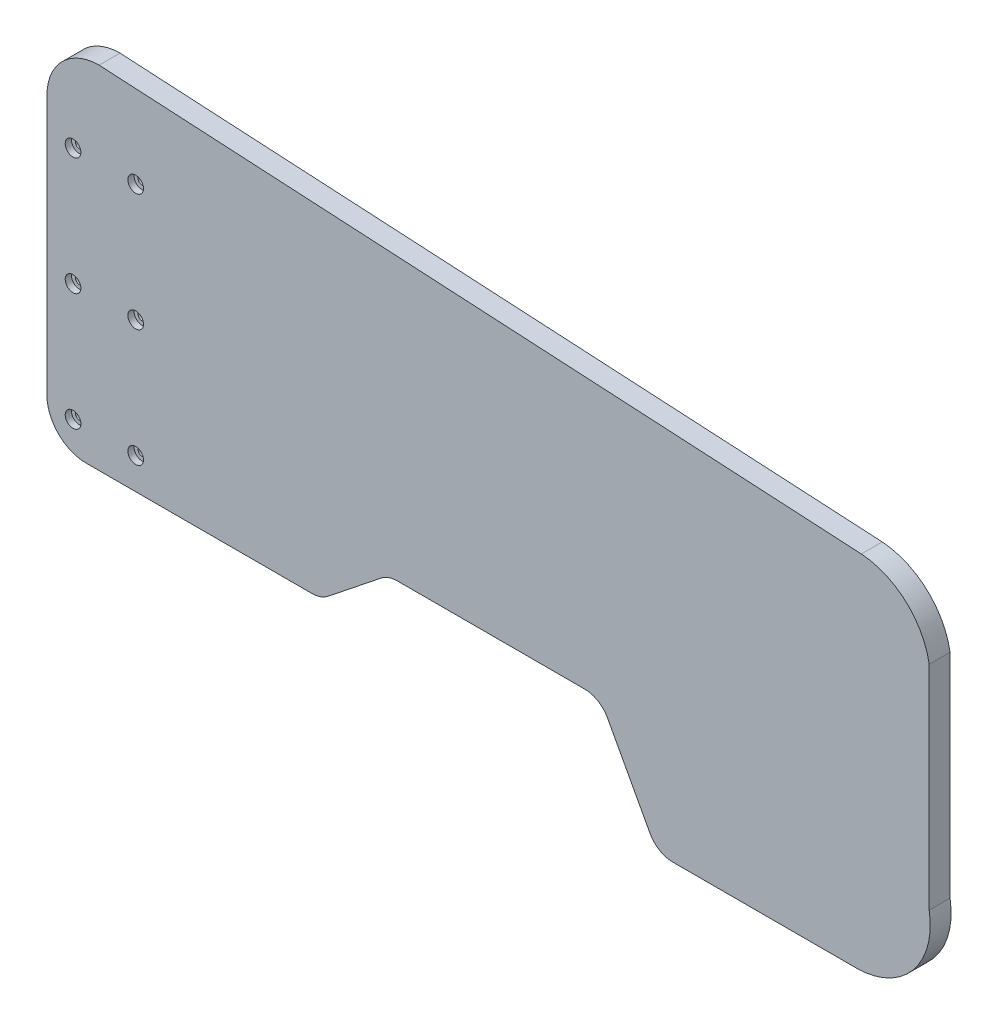
SolidWorks part; units mm, degrees
other "Folder spoin"
material "ABS PC"
ref_plane "Płaszczyzna przednia" through (0, 0, 0) normal (0, 0, 1) x (1, 0, 0)
ref_plane "Płaszczyzna górna" through (0, 0, 0) normal (0, 1, 0) x (1, 0, 0)
ref_plane "Płaszczyzna prawa" through (0, 0, 0) normal (1, 0, 0) x (0, 0, -1)
sketch "outer-wire" plane through (0, 0, 0) normal (0, 0, 1) x (1, 0, 0)
  line L0 (-24, -24.5302) -> (62.5, -24.5302)
  line L3 (-39, -9.5302) -> (-39, 90)
  line L4 (95.2361, -4) -> (167, -4)
  line L6 (176, -9.6411) -> (192, -39.2805)
  line L7 (68.7361, -22.3476) -> (89, -6.1826)
  line L10 (271, -44.5302) -> (200.7997, -44.5302)
  line L12 (299, -11.3778) -> (299, 70.2365)
  line L14 (-19, 110) -> (273, 93.8273)
  arc A0 (-39, -9.5302) -> (-24, -24.5302) centre (-24, -9.5302) ccw
  arc A1 (-19, 110) -> (-39, 90) centre (-19, 90) ccw
  arc A2 (62.5, -24.5302) -> (68.7361, -22.3476) centre (62.5, -14.5302) ccw
  arc A3 (89, -6.1826) -> (95.2361, -4) centre (95.2361, -14) cw
  arc A4 (271, -44.5302) -> (299, -11.3778) centre (271, -16.1298) ccw
  arc A5 (299, 70.2365) -> (273, 93.8273) centre (271, 65.5) ccw
  arc A6 (200.7997, -44.5302) -> (192, -39.2805) centre (200.7997, -34.5302) cw
  arc A7 (176, -9.6411) -> (167, -4) centre (167, -14) ccw
  point P14 (66, -24.5302)
  dimension "D2" = 20
  dimension "D1" = 15
  dimension "D7" = 66
  dimension "D8" = 89
  dimension "D10" = 167
  dimension "D17" = 271
  dimension "D18" = 273
  dimension "D20" = 39
  dimension "D21" = 110
  dimension "D4" = 28.4004
  dimension "D6" = 62.5
  dimension "D9" = 167
  dimension "D12" = 192
  dimension "D11" = 176
  dimension "D3" = 10
  dimension "D5" = 28.3978
  dimension "D13" = 65.5
  dimension "D14" = 4
  dimension "D15" = 71.7639
  dimension "D16" = 271
  dimension "D19" = 299
extrude "Dodanie-wyciągnięcie1" add sketch "outer-wire" along normal blind 8 contours L0 A2 L7 A3 L4 A7 L6 A6 L10 A4 L12 A5 L14 A1 L3 A0
ref_plane "Płaszczyzna6" through (0, -24.5302, 0) normal (0, -1, 0) x (-1, 0, 0)
sketch "Szkic1" plane through (0, -24.5302, 0) normal (0, -1, 0) x (-1, 0, 0)
  line L0 (24, 0) -> (-62.5, 0) construction
  line L1 (24, -8) -> (24, 0) construction
  circle A0 centre (19, 0) radius 3.5
  dimension "D1" = 7
  dimension "D2" = 5
extrude "Wytnij-wyciągnięcie1" cut sketch "Szkic1" against normal blind 100
ref_plane "Płaszczyzna12" through (0, 0, 8) normal (0, 0, 1) x (1, 0, 0)
sketch "Szkic3" plane through (0, 0, 8) normal (0, 0, 1) x (1, 0, 0)
  circle A2 centre (-5, 77.5) radius 1.5
  circle A3 centre (-29, 77.5) radius 1.5
  circle A4 centre (-29, -12.5) radius 1.5
  circle A5 centre (-29, 32.5) radius 1.5
  circle A6 centre (-5, 32.5) radius 1.5
  circle A7 centre (-5, -12.5) radius 1.5
  dimension "D6" = 45
  dimension "D2" = 12.5
  dimension "D3" = 24
  dimension "D4" = 45
  dimension "D5" = 45
  dimension "D7" = 5
extrude "Wytnij-wyciągnięcie3" cut sketch "Szkic3" along direction (0, 0, 1) on the side against the normal blind 5 contours A4 | A5 | A3 | A2 | A6 | A7
ref_plane "Płaszczyzna13" through (0, 0, 8) normal (0, 0, 1) x (1, 0, 0)
sketch "Szkic5" plane through (0, 0, 8) normal (0, 0, 1) x (1, 0, 0)
  circle A0 centre (-29, -12.5) radius 3
  circle A1 centre (-29, 32.5) radius 3
  circle A2 centre (-29, 77.5) radius 3
  circle A3 centre (-5, 77.5) radius 3
  circle A4 centre (-5, 32.5) radius 3
  circle A5 centre (-5, -12.5) radius 3
  dimension "D2" = 24
  dimension "D3" = 45
  dimension "D4" = 45
extrude "Wytnij-wyciągnięcie4" cut sketch "Szkic5" against normal blind 2.4 contours A2 | A1 | A0 | A5 | A4 | A3
